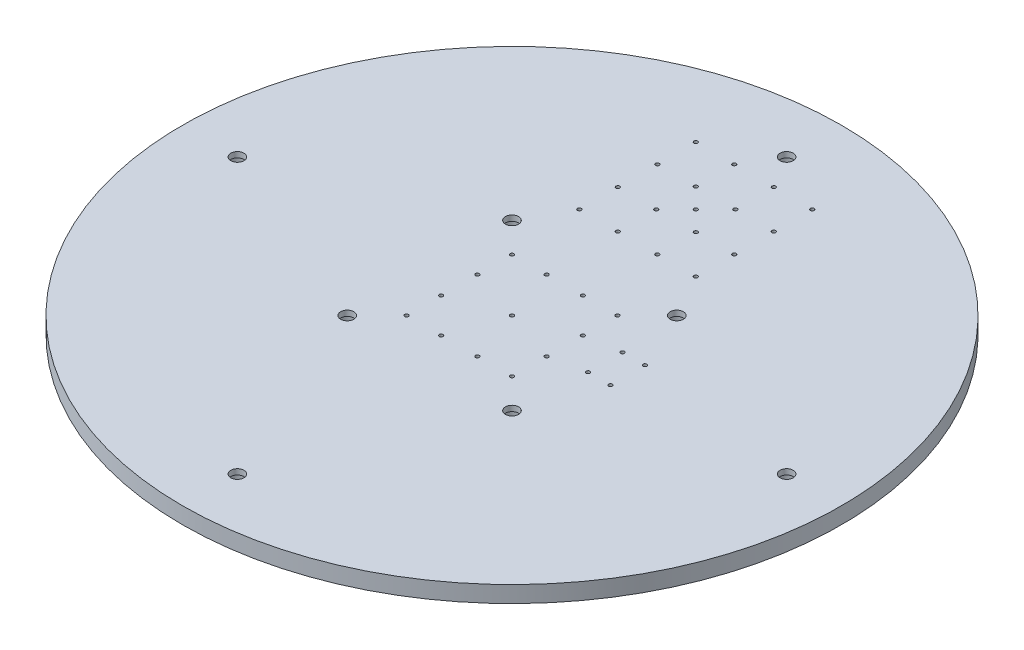
SolidWorks part; units mm, degrees
ref_plane "Front Plane" through (0, 0, 0) normal (0, 0, 1) x (1, 0, 0)
ref_plane "Top Plane" through (0, 0, 0) normal (0, 1, 0) x (1, 0, 0)
ref_plane "Right Plane" through (0, 0, 0) normal (1, 0, 0) x (0, 0, -1)
sketch "Sketch1" plane through (0, 0, 0) normal (0, 1, 0) x (1, 0, 0)
  circle A0 centre (0, 0) radius 300
  dimension "D1" = 600
extrude "Boss-Extrude1" add sketch "Sketch1" along normal blind 15
sketch "Extrusion Hole locations" plane through (0, 0, 0) normal (0, 1, 0) x (1, 0, 0)
  line L1 (75, -75) -> (-75, -75) construction
  line L2 (75, -75) -> (75, 75) construction
  line L3 (75, 75) -> (-75, 75) construction
  line L4 (-75, -75) -> (-75, 75) construction
  line L5 (75, -75) -> (-75, 75) construction
  line L6 (75, 75) -> (-75, -75) construction
  point P3 (0, 250)
  point P14 (250, 0)
  point P15 (0, -250)
  point P16 (-250, 0)
  point P105 (75, 75)
  point P108 (-75, 75)
  point P111 (-75, -75)
  point P114 (75, -75)
  dimension "D1" = 150
  dimension "D2" = 250
  dimension "D4" = 4
hole_wizard "CBORE for M10 SHCS1" positions "Extrusion Hole locations" profile "Sketch3" counterbore size "M10" standard "ANSI Metric" end condition through all
sketch "Sketch3" plane through (75, 0, 75) normal (1, 0, 0) x (0, 0, -1)
  line L0 (0, 0) -> (0, 15)
  line L1 (0, 15) -> (6, 15)
  line L3 (6, 15) -> (6, 10)
  line L4 (6, 10) -> (9, 10)
  line L5 (9, 10) -> (9, 0)
  line L7 (9, 0) -> (0, 0)
  line L11 (0, -6.35) -> (0, 107.95) construction
  dimension "Thru Hole Dia." = 12
  dimension "Thru Hole Depth" = 15
  dimension "C'Bore Dia." = 18
  dimension "C'Bore Depth" = 10
hole_wizard "CBORE for M3 SHCS1" positions "Sketch6" profile "Sketch7" counterbore size "M3" standard "ANSI Metric"
sketch "Sketch6" plane through (0, 0, 0) normal (0, -1, 0) x (-1, 0, 0)
  point P0 (0, 0)
  point P1 (0, 0)
  point P2 (-48, -48)
  point P3 (-48, -48)
  point P4 (16.5, -48)
  point P5 (-16.5, -48)
  point P6 (-16.5, -48)
  point P7 (48, -48)
  point P8 (48, -16.5)
  point P9 (48, 16.5)
  point P10 (48, 48)
  point P11 (16.5, 48)
  point P12 (-16.5, 48)
  point P13 (-48, 48)
  point P14 (0, 0)
  point P15 (0, 0)
  point P16 (-79.35, -10.1)
  point P17 (-99.7, -10.1)
  point P18 (-99.7, 21.3)
  point P19 (-79.35, 21.3)
  point P20 (-48, -16.5)
  point P21 (-48, 16.5)
sketch "Sketch7" plane through (0, 0, 0) normal (1, 0, 0) x (0, 0, -1)
  line L0 (0, 0) -> (0, 15)
  line L1 (0, 15) -> (1.7, 15)
  line L2 (1.7, 15) -> (1.7, 4)
  line L3 (1.7, 4) -> (3.25, 4)
  line L4 (3.25, 4) -> (3.25, 0)
  line L5 (3.25, 0) -> (0, 0)
  line L6 (0, -6.35) -> (0, 107.95) construction
  dimension "Thru Hole Dia." = 3.4
  dimension "Thru Hole Depth" = 15
  dimension "C'Bore Dia." = 6.5
  dimension "C'Bore Depth" = 4
hole_wizard "CBORE for M3 SHCS2" positions "Sketch8" profile "Sketch9" counterbore size "M3" standard "ANSI Metric"
sketch "Sketch8" plane through (0, 0, 0) normal (0, -1, 0) x (-1, 0, 0)
  point P0 (0, 167.3209)
  point P1 (0, 167.3209)
  point P2 (0, 167.3209)
  point P3 (53, 114.3209)
  point P4 (53, 149.3209)
  point P5 (53, 185.3209)
  point P6 (53, 220.3209)
  point P7 (18, 220.3209)
  point P8 (-18, 220.3209)
  point P9 (-53, 220.3209)
  point P10 (-53, 185.3209)
  point P11 (-53, 149.3209)
  point P12 (-53, 114.3209)
  point P13 (-18, 114.3209)
  point P14 (18, 114.3209)
  point P15 (18, 149.3209)
  point P16 (18, 185.3209)
  point P17 (-18, 149.3209)
  point P18 (-18, 185.3209)
sketch "Sketch9" plane through (0, 0, -167.3209) normal (1, 0, 0) x (0, 0, -1)
  line L0 (0, 0) -> (0, 15)
  line L1 (0, 15) -> (1.7, 15)
  line L2 (1.7, 15) -> (1.7, 4)
  line L3 (1.7, 4) -> (3.25, 4)
  line L4 (3.25, 4) -> (3.25, 0)
  line L5 (3.25, 0) -> (0, 0)
  line L6 (0, -6.35) -> (0, 107.95) construction
  dimension "Thru Hole Dia." = 3.4
  dimension "Thru Hole Depth" = 15
  dimension "C'Bore Dia." = 6.5
  dimension "C'Bore Depth" = 4
